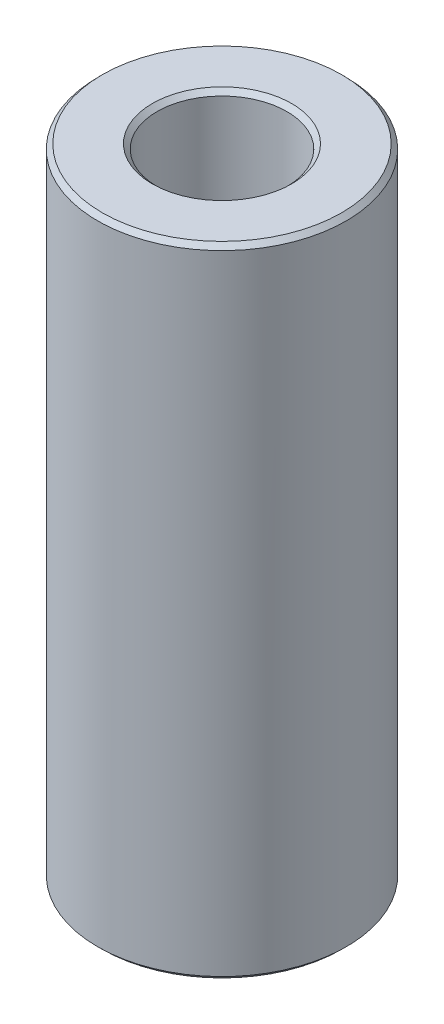
SolidWorks part; units mm, degrees
ref_plane "Front Plane" through (0, 0, 0) normal (0, 0, 1) x (1, 0, 0)
ref_plane "Top Plane" through (0, 0, 0) normal (0, 1, 0) x (1, 0, 0)
ref_plane "Right Plane" through (0, 0, 0) normal (1, 0, 0) x (0, 0, -1)
sketch "Sketch1" plane through (0, 0, 0) normal (0, 1, 0) x (1, 0, 0)
  circle A0 centre (0, 0) radius 50
  dimension "SLEEVE_OD" = 100
extrude "Boss-Extrude1" add sketch "Sketch1" along normal blind 256.7258
sketch "Sketch2" plane through (0, 0, 0) normal (0, 1, 0) x (1, 0, 0)
  circle A0 centre (0, 0) radius 26.1283
  dimension "BORE_D" = 52.2567
extrude "Cut-Extrude1" cut sketch "Sketch2" along normal through all
chamfer "Chamfer1" distance 1.913 angle 44.022 4 edges at (0, 256.7258, 26.1283) (0, 0, 26.1283) (0, 0, 50) (0, 256.7258, 50) first distance on face at (0, 256.7258, 26.1283) first distance on face at (0, 0, 26.1283) first distance on face at (0, 256.7258, 50)
